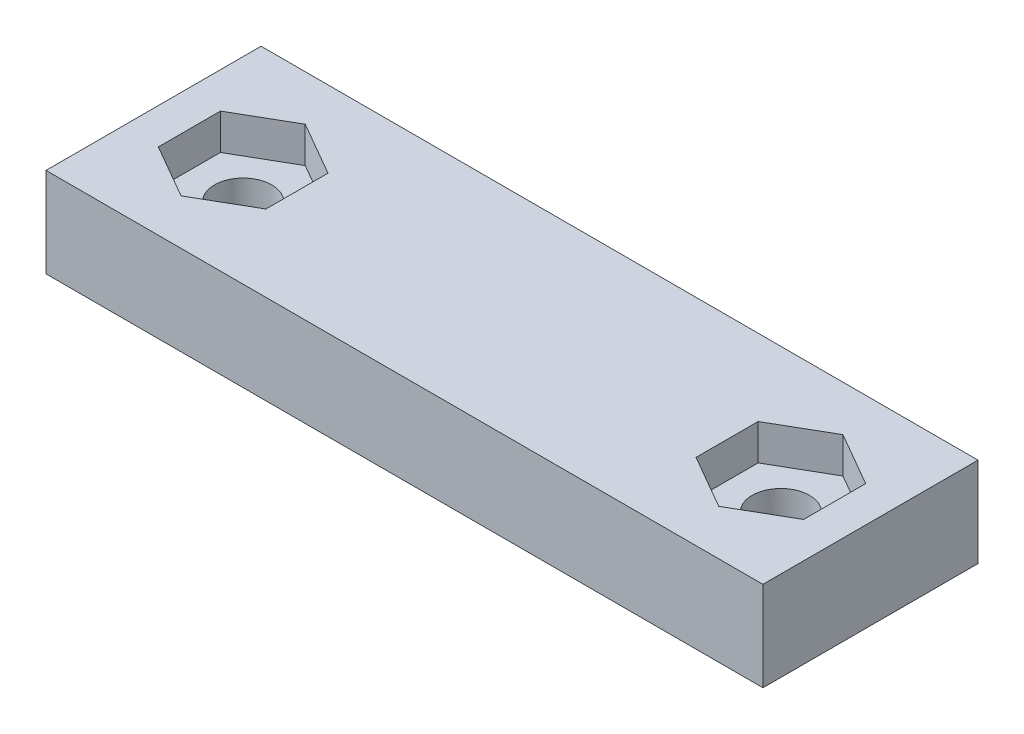
SolidWorks part; units mm, degrees
ref_plane "Front Plane" through (0, 0, 0) normal (0, 0, 1) x (1, 0, 0)
ref_plane "Top Plane" through (0, 0, 0) normal (0, 1, 0) x (1, 0, 0)
ref_plane "Right Plane" through (0, 0, 0) normal (1, 0, 0) x (0, 0, -1)
sketch "Sketch1" plane through (0, 0, 0) normal (0, 1, 0) x (1, 0, 0)
  line L1 (-20, 6) -> (20, 6)
  line L2 (-20, 6) -> (-20, -6)
  line L3 (-20, -6) -> (20, -6)
  line L4 (20, 6) -> (20, -6)
  line L5 (-20, 6) -> (20, -6) construction
  line L6 (-20, -6) -> (20, 6) construction
  point P0 (0, 0)
  dimension "D1" = 40
  dimension "D2" = 12
extrude "Boss-Extrude1" add sketch "Sketch1" along normal blind 5
sketch "Sketch2" plane through (0, 5, 0) normal (0, 1, 0) x (1, 0, 0)
  line L0 (-20, 0) -> (20, 0) construction
  line L1 (-20, 6) -> (-20, -6) construction
  line L2 (20, -6) -> (20, 6) construction
  line L3 (0, -6) -> (0, 7.5) construction
  line L4 (-20, -6) -> (20, -6) construction
  line L5 (20, 6) -> (-20, 6) construction
  circle A0 centre (15, 0) radius 1.6
  circle A1 centre (-15, 0) radius 1.6
  point P17 (0, 6)
  dimension "D1" = 3.2
  dimension "D2" = 15
extrude "Cut-Extrude2" cut sketch "Sketch2" against normal through all
sketch "Sketch3" plane through (-20, 0, 0) normal (-1, 0, 0) x (0, 0, 1)
  line L0 (-5.25, 1) -> (-5.25, 0)
  line L2 (-5.25, 0) -> (-4.25, 0)
  line L3 (-4.25, 0) -> (-4.25, 1)
  line L4 (-4.25, 1) -> (-5.25, 1)
  line L5 (-3.25, 0) -> (-2.25, 0)
  line L6 (-3.25, 1) -> (-3.25, 0)
  line L7 (-2.25, 0) -> (-2.25, 1)
  line L8 (-2.25, 1) -> (-3.25, 1)
  line L9 (-1.25, 0) -> (-0.25, 0)
  line L10 (-1.25, 1) -> (-1.25, 0)
  line L11 (-0.25, 0) -> (-0.25, 1)
  line L12 (-0.25, 1) -> (-1.25, 1)
  line L13 (0.75, 0) -> (1.75, 0)
  line L14 (0.75, 1) -> (0.75, 0)
  line L15 (1.75, 0) -> (1.75, 1)
  line L16 (1.75, 1) -> (0.75, 1)
  line L17 (2.75, 0) -> (3.75, 0)
  line L18 (2.75, 1) -> (2.75, 0)
  line L19 (3.75, 0) -> (3.75, 1)
  line L20 (3.75, 1) -> (2.75, 1)
  line L21 (4.75, 0) -> (5.75, 0)
  line L22 (4.75, 1) -> (4.75, 0)
  line L23 (5.75, 0) -> (5.75, 1)
  line L24 (5.75, 1) -> (4.75, 1)
  line L25 (6.75, 0) -> (7.75, 0)
  line L26 (6.75, 1) -> (6.75, 0)
  line L27 (7.75, 0) -> (7.75, 1)
  line L28 (7.75, 1) -> (6.75, 1)
  line L29 (8.75, 0) -> (9.75, 0)
  line L30 (8.75, 1) -> (8.75, 0)
  line L31 (9.75, 0) -> (9.75, 1)
  line L32 (9.75, 1) -> (8.75, 1)
  line L33 (-6, 5) -> (-6, 0) construction
  line L34 (-6, 0) -> (6, 0) construction
  dimension "D1" = 1
  dimension "D3" = 0.75
  dimension "D4" = 1
  dimension "D5" = 1
  dimension "D6" = 0
  dimension "D7" = 1
  dimension "D2" = 8
extrude "Teeth" cut sketch "Sketch3" against normal blind 5 and the other way blind 5 from surface starting at plane "Right Plane"
sketch "Sketch4" plane through (0, 5, 0) normal (0, 1, 0) x (1, 0, 0)
  line L0 (-15, 0) -> (-15, 3.4641) construction
  line L1 (-15, 3.4641) -> (-18, 1.7321)
  line L2 (-18, 1.7321) -> (-18, -1.7321)
  line L3 (-18, -1.7321) -> (-15, -3.4641)
  line L4 (-15, -3.4641) -> (-12, -1.7321)
  line L5 (-12, -1.7321) -> (-12, 1.7321)
  line L6 (-12, 1.7321) -> (-15, 3.4641)
  line L7 (0, 6) -> (0, -7.5) construction
  line L8 (20, 6) -> (-20, 6) construction
  line L10 (15, 0) -> (15, 3.4641) construction
  line L11 (12, 1.7321) -> (15, 3.4641)
  line L12 (12, -1.7321) -> (12, 1.7321)
  line L13 (15, -3.4641) -> (12, -1.7321)
  line L14 (18, -1.7321) -> (15, -3.4641)
  line L15 (18, 1.7321) -> (18, -1.7321)
  line L16 (15, 3.4641) -> (18, 1.7321)
  line L17 (-15, 0) -> (-15, 3.4641) construction
  circle A0 centre (-15, 0) radius 3 construction
  circle A1 centre (15, 0) radius 3 construction
  dimension "D1" = 6
extrude "Cut-Extrude4" cut sketch "Sketch4" against normal blind 2
equation "\"X-ROD-SPACING\"=45"
equation "\"Y-ROD-SPACING\"=75"
equation "\"Z-ROD-SPACING\"=17.5"
equation "\"Y-BED-OFFSET\"=2"
equation "\"Y-BED-ROD-INSET\"=3.5"
equation "\"T-SLOT-NUT-FILLET-RADIUS\"=0.25"
equation "\"T-SLOT-SCREW-SHAFT-RADIUS\"=1.75"
equation "\"T-SLOT-SCREW-SHAFT-CUTOUT-LENGTH\"=10.5"
equation "\"T-SLOT-NUT-DEPTH\"=4.2"
equation "\"T-SLOT-NUT-WIDTH\"=3"
equation "\"T-SLOT-NUT-END-DISTANCE\"=8"
equation "\"ACRYLIC-THICKNESS\"=10"
equation "\"ACRYLIC-THICKNESS2\"=4.5"
equation "\"ACRYLIC-TAB-CUTOUT-SIZE\"=\"ACRYLIC-THICKNESS\"+\"ACRYLIC-TAB-TOLERANCE\"*2"
equation "\"ACRYLIC-TAB-WIDTH\"=\"ACRYLIC-THICKNESS\""
equation "\"ACRYLIC-M3-HOLE\"=3.2"
equation "\"SMOOTHROD-CAP-SCREW-DISTANCE\"=20"
equation "\"FRAME-WIDTH-INNER\"=370"
equation "\"NEMA17-HOLE-SPACING\"=31"
equation "\"NEMA17-CENTRAL-CUTOUT\"=22.5"
equation "\"Z-BRACKET-REACH\"=55"
equation "\"TOP-BRACKET-SPACING\"=40"
equation "\"SMOOTHROD-X-LENGTH\"=350"
equation "\"SMOOTHROD-Y-LENGTH\"=350"
equation "\"SMOOTHROD-Z-LENGTH\"=350"
equation "\"SMOOTHROD-TIGHTENING-HEADROOM\"=1"
equation "\"LEADSCREW-Z-LENGTH\"=300"
equation "\"SCREW-LENGTH-FRAME\"=\"ACRYLIC-THICKNESS\" + 10"
equation "\"SCREW-HEAD-RADIUS\"=6"
equation "\"PRINTED-X-SMOOTHROD-DIAMETER\"=8.2"
equation "\"PRINTED-X-SMOOTHROD-CUTOUT\"=10"
equation "\"PRINTED-X-BASE-HEIGHT\"=10"
equation "\"PRINTED-LM8UU-CUTOUT-SIZE\"=15.25"
equation "\"PRINTED-LM8UU-CUTOUT-LENGTH\"=24.5"
equation "\"PRINTED-X-IDLER-HEIGHT\"=16"
equation "\"PSU-MOUNTING-WIDTH\"=95"
equation "\"PSU-MOUNTING-HEIGHT\"=177"
equation "\"Y-BELT-TO-ROD-DISTANCE\"=20"
equation "\"D1@Sketch4\"=\"T-SLOT-NUT-WIDTH\"*2"
